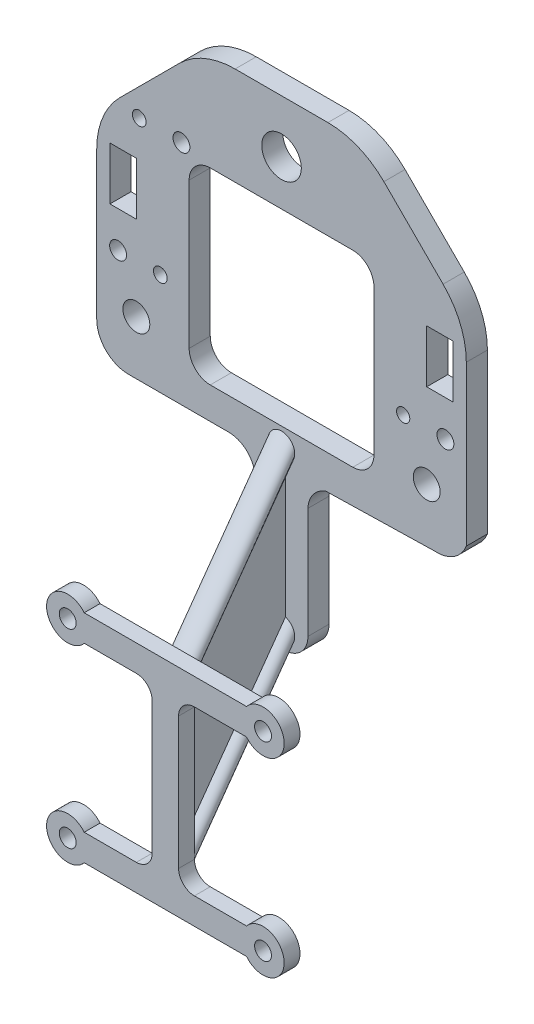
SolidWorks part; units mm, degrees
ref_plane "Спереди" through (0, 0, 0) normal (0, 0, 1) x (1, 0, 0)
ref_plane "Сверху" through (0, 0, 0) normal (0, 1, 0) x (1, 0, 0)
ref_plane "Справа" through (0, 0, 0) normal (1, 0, 0) x (0, 0, -1)
sketch "Model" plane through (0, 0, 0) normal (0, 0, 1) x (1, 0, 0)
  line L0 (-32.5, 1.0025) -> (-27.5, 1.0025)
  line L1 (-27.5, 1.0025) -> (-27.5, 11.0025)
  line L2 (-27.5, 11.0025) -> (-32.5, 11.0025)
  line L3 (-32.5, 11.0025) -> (-32.5, 1.0025)
  line L4 (32.5, 11.0025) -> (27.5, 11.0025)
  line L5 (27.5, 11.0025) -> (27.5, 1.0025)
  line L6 (27.5, 1.0025) -> (32.5, 1.0025)
  line L7 (32.5, 1.0025) -> (32.5, 11.0025)
  line L8 (-8.7868, 34.9967) -> (8.7868, 34.9967)
  line L9 (35, 8.7835) -> (35, -21.3839)
  line L11 (5, -30.1878) -> (5, -51.1878)
  line L12 (0.5, -55.6878) -> (-0.5, -55.6878)
  line L13 (-5, -51.1878) -> (-5, -30.1878)
  line L14 (8.4254, -25.669) -> (29, -25.1878)
  line L16 (-15.452, -19.1878) -> (15.452, -19.1878)
  line L17 (-17.5, -3.7682) -> (-17.5, -19.1878) construction
  line L18 (-17.5, -19.1878) -> (-15.452, -19.1878) construction
  line L19 (17.5, 14.8517) -> (17.5, 16.4118) construction
  line L20 (-27.5, 24.9967) -> (27.5, 24.9967) construction
  line L21 (17.5, 16.4118) -> (11.2964, 16.4118) construction
  line L22 (-27.5, 24.9967) -> (-27.5, -15.0033) construction
  line L23 (27.5, 24.9967) -> (27.5, -15.0033) construction
  line L24 (-17.5, -19.1878) -> (17.5, -19.1878)
  line L25 (-17.5, -19.1878) -> (-17.5, 16.4118)
  line L26 (-27.5, -15.0033) -> (27.5, -15.0033) construction
  line L27 (-17.5, 16.4118) -> (17.5, 16.4118)
  line L28 (17.5, -19.1878) -> (17.5, 16.4118)
  line L29 (-10, 16.0025) -> (10, 16.0025) construction
  line L30 (0, -15.0033) -> (0, -40.6878) construction
  line L31 (-5, -40.6878) -> (5, -40.6878) construction
  line L32 (0, -40.6878) -> (0, -51.1878) construction
  line L33 (0, -51.1878) -> (-0.5, -51.1878) construction
  line L34 (0, -51.1878) -> (0.5, -51.1878) construction
  line L35 (-10, -30.1878) -> (-0.5, -30.1878) construction
  line L36 (-0.5, -30.1878) -> (-0.5, -51.1878) construction
  line L37 (-30.6066, 19.3901) -> (-19.3934, 30.6033)
  line L38 (-35, 14.9967) -> (-35, 34.9967) construction
  line L39 (-35, 34.9967) -> (-15, 34.9967) construction
  line L40 (30.6066, 19.3901) -> (19.3934, 30.6033)
  line L41 (0, 34.9967) -> (0, 24.9967) construction
  line L42 (-35, 8.7835) -> (-35, -19.1878)
  line L43 (-29, -25.1878) -> (-10, -25.1878)
  line L44 (-32.5, 6.0025) -> (-27.5, 6.0025) construction
  line L45 (-30.955, -5.8427) -> (-22.955, -5.8427) construction
  line L46 (-30, 6.0025) -> (-30, -5.8427) construction
  line L47 (-30.955, 17.8476) -> (-22.955, 17.8476) construction
  line L48 (-22.955, 17.8476) -> (-18.955, 17.8476)
  circle A0 centre (-22.955, -5.8427) radius 1.3
  circle A1 centre (23.045, -5.8427) radius 1.25
  circle A2 centre (-30.955, -5.8427) radius 1.6
  circle A3 centre (31.045, -5.8427) radius 1.6
  circle A4 centre (-27.5, -15.0033) radius 2.55
  circle A5 centre (27.5, 24.9967) radius 3.556 construction
  circle A6 centre (-27.5, 24.9967) radius 3.556 construction
  circle A7 centre (27.5, -15.0033) radius 2.55
  circle A8 centre (0, 24.9967) radius 3.75
  arc A9 (35, 8.7835) -> (30.6066, 19.3901) centre (20, 8.7835) ccw
  arc A10 (-35, 8.7835) -> (-30.6066, 19.3901) centre (-20, 8.7835) cw
  arc A11 (19.3934, 30.6033) -> (8.7868, 34.9967) centre (8.7868, 19.9967) ccw
  arc A12 (-19.3934, 30.6033) -> (-8.7868, 34.9967) centre (-8.7868, 19.9967) cw
  arc A13 (-35, -19.1878) -> (-29, -25.1878) centre (-29, -19.1878) ccw
  circle A14 centre (-26.955, 17.8476) radius 1.3
  circle A15 centre (-18.955, 17.8476) radius 1.6
  arc A104 (29, -25.1878) -> (35, -21.3839) centre (29.4108, -19.2019) ccw
  arc A105 (8.4254, -25.669) -> (5, -30.1878) centre (9.9948, -30.4163) ccw
  arc A106 (0.5, -55.6878) -> (5, -51.1878) centre (0.5, -51.1878) ccw
  arc A107 (-5, -51.1878) -> (-0.5, -55.6878) centre (-0.5, -51.1878) ccw
  arc A108 (-5, -30.1878) -> (-10, -25.1878) centre (-10, -30.1878) ccw
  point P29 (6.0102, -27.3959)
  point P38 (35, 14.9967)
  point P44 (15, 34.9967)
  dimension "D1" = 7.112
  dimension "D2" = 7.5
  dimension "D6" = 5
  dimension "D7" = 4.5
  dimension "D8" = 4.5
  dimension "D12" = 15
  dimension "D14" = 6
  dimension "D15" = 6
  dimension "D16" = 2.6
  dimension "D19" = 3.2
  dimension "D20" = 3.2
  dimension "D21" = 2.6
  dimension "D3" = 40
  dimension "D4" = 10
  dimension "D5" = 5
  dimension "D9" = 21
  dimension "D10" = 20
  dimension "D11" = 20
  dimension "D13" = 10
  dimension "D17" = 8
  dimension "D18" = 4
extrude "Бобышка-Вытянуть1" add sketch "Model" along normal blind 4 contours A108 L13 A107 L12 A106 L11 A105 L14 A104 L9 L8 L3 L2 L1 L0 L7 L6 L5 L4 L28 L24 L16 L25 L27 A0 A1 A2 A3 A4 A5 A6 A7 region at (0, 33.8511, 0)
sketch "Эскиз1" plane through (0, 0, 4) normal (0, 0, 1) x (1, 0, 0)
  line L0 (-27.5, -15.0033) -> (27.5, -15.0033) construction
  line L1 (0, -15.0033) -> (0, -22.5033) construction
  line L2 (0, -22.5033) -> (0, -52.5033) construction
  line L3 (0, -37.5033) -> (0.75, -37.5033) construction
  line L5 (0.75, -50.1185) -> (0.75, -24.8882)
  line L6 (-0.75, -50.1185) -> (-0.75, -24.8882)
  arc A0 (0.75, -24.8882) -> (-0.75, -24.8882) centre (0, -22.5033) ccw
  arc A1 (0.75, -50.1185) -> (-0.75, -50.1185) centre (0, -52.5033) cw
  point P14 (-0.75, -37.5033)
  dimension "D3" = 5
  dimension "D1" = 7.5
  dimension "D2" = 30
  dimension "D4" = 0.75
sketch "Эскиз2" plane through (0, 0, 0) normal (1, 0, 0) x (0, 0, -1)
  line L0 (-4, -22.5033) -> (-4, -49.0033) construction
  line L1 (-4, -49.0033) -> (-23, -49.0033) construction
  line L2 (-4, -22.5033) -> (-23, -49.0033) construction
  dimension "D1" = 26.5
  dimension "D2" = 19
sketch "Эскиз3" plane through (0, 0, 0) normal (1, 0, 0) x (0, 0, -1)
  line L0 (-4, -22.5033) -> (-23, -49.0033) construction
extrude "Бобышка-Вытянуть2" add sketch "Эскиз1" along direction (0, -0.8127, 0.5827) on the side of the normal up to vertex (19 mm away) up to point (0, -49.0033, 23)
sketch "Эскиз4" plane through (0, 0, 23) normal (0, 0, 1) x (1, 0, 0)
  line L0 (0, -49.0033) -> (0, -79.0033) construction
  line L1 (0, -49.0033) -> (18.5, -49.0033) construction
  line L2 (9.25, -49.0033) -> (9.25, -51.5033) construction
  line L3 (15.3775, -51.5033) -> (5.5, -51.5033)
  line L4 (15.3775, -46.5033) -> (-15.3775, -46.5033)
  line L5 (0, -64.0033) -> (2.5, -64.0033) construction
  line L6 (2.5, -54.5033) -> (2.5, -64.0033)
  line L7 (-2.5, -54.5033) -> (-2.5, -64.0033)
  line L8 (-15.3775, -51.5033) -> (-5.5, -51.5033)
  line L9 (0, -67.0033) -> (7.4707, -67.0033) construction
  line L10 (7.4707, -67.0033) -> (7.4707, -49.0033) construction
  line L11 (-15.3775, -82.5033) -> (-5.5, -82.5033)
  line L12 (15.3775, -82.5033) -> (5.5, -82.5033)
  line L13 (15.3775, -87.5033) -> (-15.3775, -87.5033)
  line L14 (-2.5, -64.0033) -> (-2.5, -79.5033)
  line L15 (2.5, -64.0033) -> (2.5, -79.5033)
  arc A0 (15.3775, -51.5033) -> (15.3775, -46.5033) centre (18.5, -49.0033) ccw
  circle A1 centre (18.5, -49.0033) radius 1.6
  arc A2 (2.5, -54.5033) -> (5.5, -51.5033) centre (5.5, -54.5033) cw
  arc A3 (-2.5, -54.5033) -> (-5.5, -51.5033) centre (-5.5, -54.5033) ccw
  circle A4 centre (-18.5, -49.0033) radius 1.6
  arc A5 (-15.3775, -51.5033) -> (-15.3775, -46.5033) centre (-18.5, -49.0033) cw
  circle A6 centre (-18.5, -85.0033) radius 1.6
  arc A7 (-2.5, -79.5033) -> (-5.5, -82.5033) centre (-5.5, -79.5033) cw
  arc A8 (2.5, -79.5033) -> (5.5, -82.5033) centre (5.5, -79.5033) ccw
  circle A9 centre (18.5, -85.0033) radius 1.6
  arc A10 (15.3775, -82.5033) -> (15.3775, -87.5033) centre (18.5, -85.0033) cw
  arc A11 (-15.3775, -82.5033) -> (-15.3775, -87.5033) centre (-18.5, -85.0033) ccw
  point P25 (0, -46.5033)
  dimension "D2" = 8
  dimension "D3" = 3.2
  dimension "D6" = 3
  dimension "D1" = 18.5
  dimension "D4" = 2.5
  dimension "D5" = 2.5
  dimension "D7" = 18
extrude "Бобышка-Вытянуть3" add sketch "Эскиз4" along normal blind 3
fillet "Скругление1" radius 4 4 edges at (-17.5, 16.4118, 2) (17.5, 16.4118, 2) (17.5, -19.1878, 2) (-17.5, -19.1878, 2)
